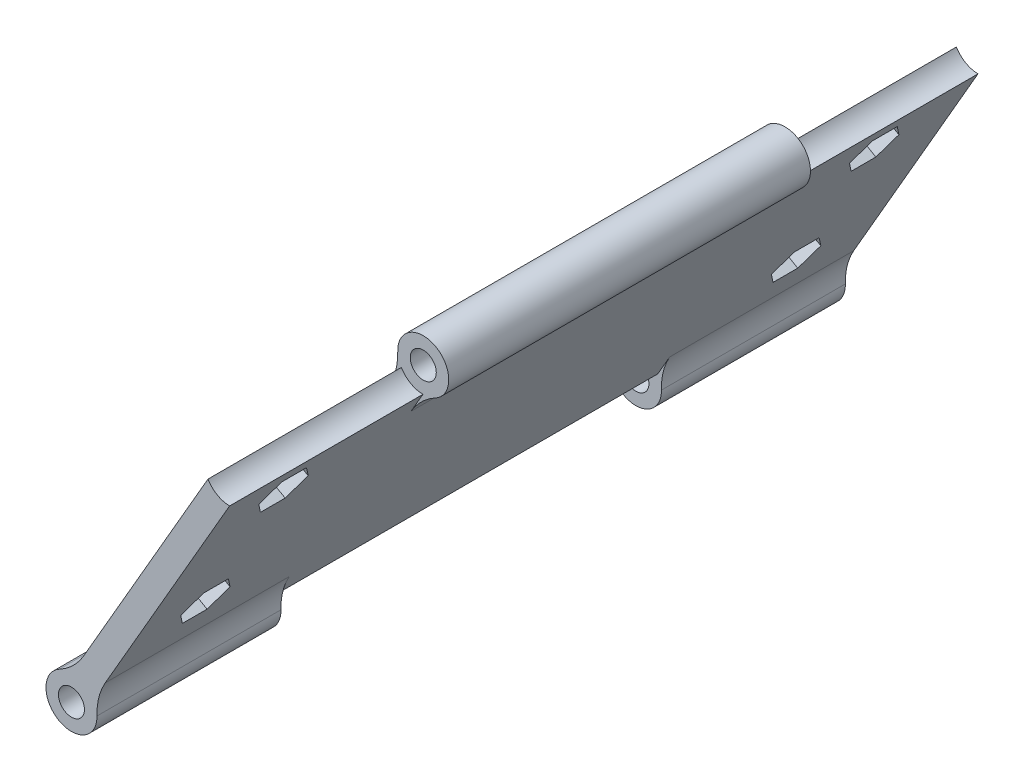
SolidWorks part; units mm, degrees
material "PLA"
ref_plane "Front Plane" through (0, 0, 0) normal (0, 0, 1) x (1, 0, 0)
ref_plane "Top Plane" through (0, 0, 0) normal (0, 1, 0) x (1, 0, 0)
ref_plane "Right Plane" through (0, 0, 0) normal (1, 0, 0) x (0, 0, -1)
sketch "Sketch2" plane through (0, 0, 0) normal (0, 0, 1) x (1, 0, 0)
  line L0 (0, 0) -> (38.1, 0)
  line L1 (0, 0) -> (0, -38.1)
  circle A0 centre (0, 0) radius 38.1
  circle A1 centre (0, -29.337) radius 1.5875
  circle A2 centre (-25.4066, 14.6685) radius 1.5875
  circle A3 centre (25.4066, 14.6685) radius 1.5875
  point P13 (0, 0)
  dimension "D1" = 76.2
  dimension "D2" = 3.175
  dimension "D3" = 8.763
  dimension "D4" = 3
extrude "Boss-Extrude1" add sketch "Sketch2" along normal blind 10 contours A1 L1 L0 A0 A3 A2 | A1 L1 A0 L0 region at (-5.4206, 5.3873, 0) region at (16.2241, -16.1243, 0)
sketch "Sketch3" plane through (0, 0, 10) normal (0, 0, 1) x (1, 0, 0)
  line L1 (0, -29.337) -> (25.4066, 14.6685)
  line L2 (1.7321, -30.337) -> (27.1386, 13.6685)
  line L3 (-1.7321, -28.337) -> (23.6745, 15.6685)
  circle A11 centre (0, -29.337) radius 1.5875
  circle A12 centre (25.4066, 14.6685) radius 1.5875
  circle A17 centre (0, -29.337) radius 2.0875
  circle A18 centre (25.4066, 14.6685) radius 2.0875
  circle A19 centre (0, -29.337) radius 4.0875
  circle A20 centre (25.4066, 14.6685) radius 4.0875
  dimension "D1" = 0.5
  dimension "D2" = 2
  dimension "D4" = 2
  dimension "D5" = 2
extrude "Boss-Extrude2" add sketch "Sketch3" along normal blind 120 separate body contours L2 A20 L3 A18 | L1 A20 L2 A18 | L3 A20 L1 A18 | A20 L1 A19 L2 | A20 L3 A19 L1 | L1 A19 L3 A17 | L2 A19 L1 A17 | L3 A19 L2 A17 region at (0.4725, -26.4041, 10) region at (2.3037, -27.4614, 10) region at (11.8338, -6.8323, 10) region at (13.5728, -7.8362, 10) region at (-1.1016, -31.245, 10) region at (23.1028, 12.7929, 10) region at (24.9341, 11.7356, 10) region at (24.355, 18.4986, 10)
delete or keep bodies "Body-Delete/Keep 2" type delete bodies bodies 101
ref_plane "Plane1" through (0, 0, 70) normal (0, 0, 1) x (1, 0, 0)
sketch "Sketch4" plane through (0, 0, 70) normal (0, 0, 1) x (1, 0, 0)
  circle A1 centre (0, -29.337) radius 4.0875
extrude "Cut-Extrude1" cut sketch "Sketch4" against normal blind 30.5 and the other way blind 30.5 contours A1
sketch "Sketch5" plane through (0, 0, 10) normal (0, 0, -1) x (-1, 0, 0)
  circle A0 centre (-25.4066, 14.6685) radius 4.0875
extrude "Cut-Extrude2" cut sketch "Sketch5" against normal offset from surface (31 mm away) 1.5 up to face at (2.0875, -29.337, 39.5) offset beyond the face yes
sketch "Sketch6" plane through (0, 0, 130) normal (0, 0, 1) x (1, 0, 0)
  circle A0 centre (25.4066, 14.6685) radius 4.0875
extrude "Cut-Extrude3" cut sketch "Sketch6" against normal offset from surface (31 mm away) 1.5 contours A0 up to face at (2.0875, -29.337, 100.5) offset beyond the face yes
fillet "Fillet1" radius 10 6 edges at (21.8921, 12.5813, 70) (0.0503, -25.2498, 24.75) (0.0503, -25.2498, 115.25) (3.5144, -27.2498, 115.25) (3.5144, -27.2498, 24.75) (25.3562, 10.5813, 70)
sketch "Sketch7" plane through (10.9712, -6.3342, 0) normal (-0.866, 0.5, 0) x (0, 0, 1)
  circle A0 centre (23.772, -8.9489) radius 1.75
  circle A1 centre (23.772, 16.0955) radius 1.75
  circle A2 centre (118.4886, 16.0955) radius 1.75
  circle A3 centre (118.4886, -8.9489) radius 1.75
  dimension "D1" = 3.5
extrude "Cut-Extrude4" cut sketch "Sketch7" against normal up to surface (4 mm away) up to face at (14.7532, -7.7836, 70)
sketch "Sketch8" plane through (14.4353, -8.3343, 0) normal (0.866, -0.5, 0) x (0, 0, -1)
  line L1 (-19.8125, 16.0955) -> (-21.7922, 19.5245)
  line L2 (-21.7922, 19.5245) -> (-25.7517, 19.5245)
  line L3 (-25.7517, 19.5245) -> (-27.7314, 16.0955)
  line L4 (-27.7314, 16.0955) -> (-25.7517, 12.6665)
  line L5 (-25.7517, 12.6665) -> (-21.7922, 12.6665)
  line L6 (-21.7922, 12.6665) -> (-19.8125, 16.0955)
  line L7 (-19.8125, -8.9489) -> (-21.7922, -5.5199)
  line L8 (-21.7922, -5.5199) -> (-25.7517, -5.5199)
  line L9 (-25.7517, -5.5199) -> (-27.7314, -8.9489)
  line L10 (-27.7314, -8.9489) -> (-25.7517, -12.3779)
  line L11 (-25.7517, -12.3779) -> (-21.7922, -12.3779)
  line L12 (-21.7922, -12.3779) -> (-19.8125, -8.9489)
  line L13 (-114.5291, 16.0955) -> (-116.5088, 19.5245)
  line L14 (-116.5088, 19.5245) -> (-120.4683, 19.5245)
  line L15 (-120.4683, 19.5245) -> (-122.448, 16.0955)
  line L16 (-122.448, 16.0955) -> (-120.4683, 12.6665)
  line L17 (-120.4683, 12.6665) -> (-116.5088, 12.6665)
  line L18 (-116.5088, 12.6665) -> (-114.5291, 16.0955)
  line L25 (-114.5291, -8.9489) -> (-116.5088, -5.5199)
  line L26 (-116.5088, -5.5199) -> (-120.4683, -5.5199)
  line L27 (-120.4683, -5.5199) -> (-122.448, -8.9489)
  line L28 (-122.448, -8.9489) -> (-120.4683, -12.3779)
  line L29 (-120.4683, -12.3779) -> (-116.5088, -12.3779)
  line L30 (-116.5088, -12.3779) -> (-114.5291, -8.9489)
  circle A0 centre (-23.772, 16.0955) radius 3.429 construction
  circle A1 centre (-23.772, -8.9489) radius 3.429 construction
  circle A2 centre (-118.4886, 16.0955) radius 3.429 construction
  circle A3 centre (-118.4886, -8.9489) radius 3.429 construction
  dimension "D1" = 6.858
extrude "Cut-Extrude5" cut sketch "Sketch8" against normal blind 2.25
